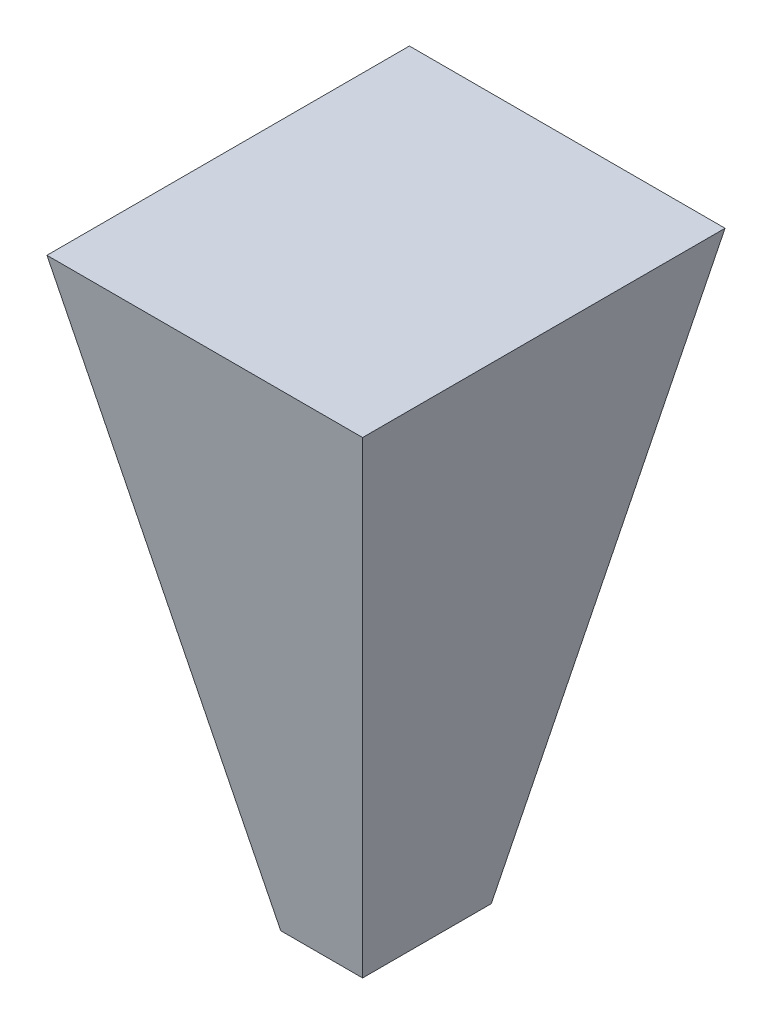
SolidWorks part; units mm, degrees
ref_plane "Front Plane" through (0, 0, 0) normal (0, 0, 1) x (1, 0, 0)
ref_plane "Top Plane" through (0, 0, 0) normal (0, 1, 0) x (1, 0, 0)
ref_plane "Right Plane" through (0, 0, 0) normal (1, 0, 0) x (0, 0, -1)
sketch "Sketch1" plane through (0, 0, 0) normal (0, 1, 0) x (1, 0, 0)
  line L1 (-3.5, 5.5) -> (3.5, 5.5)
  line L2 (-3.5, 5.5) -> (-3.5, -5.5)
  line L3 (-3.5, -5.5) -> (3.5, -5.5)
  line L4 (3.5, 5.5) -> (3.5, -5.5)
  line L5 (-3.5, 5.5) -> (3.5, -5.5) construction
  line L6 (-3.5, -5.5) -> (3.5, 5.5) construction
  point P0 (0, 0)
  dimension "D1" = 7
  dimension "D2" = 11
extrude "Boss-Extrude1" add sketch "Sketch1" along normal blind 50 draft 11.3 draft outward yes
